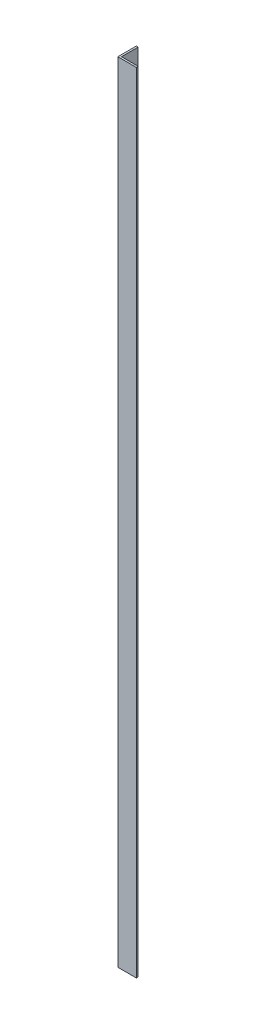
SolidWorks part; units mm, degrees
ref_plane "Спереди" through (0, 0, 0) normal (0, 0, 1) x (1, 0, 0)
ref_plane "Сверху" through (0, 0, 0) normal (0, 1, 0) x (1, 0, 0)
ref_plane "Справа" through (0, 0, 0) normal (1, 0, 0) x (0, 0, -1)
sketch "Эскиз1" plane through (0, 0, 0) normal (0, 1, 0) x (1, 0, 0)
  line L0 (0, 0) -> (50, 0)
  line L1 (0, 0) -> (0, 50)
extrude "Вытянуть-Тонкостенный1" add sketch "Эскиз1" along normal blind 2125 thin thin type one direction wall 5
